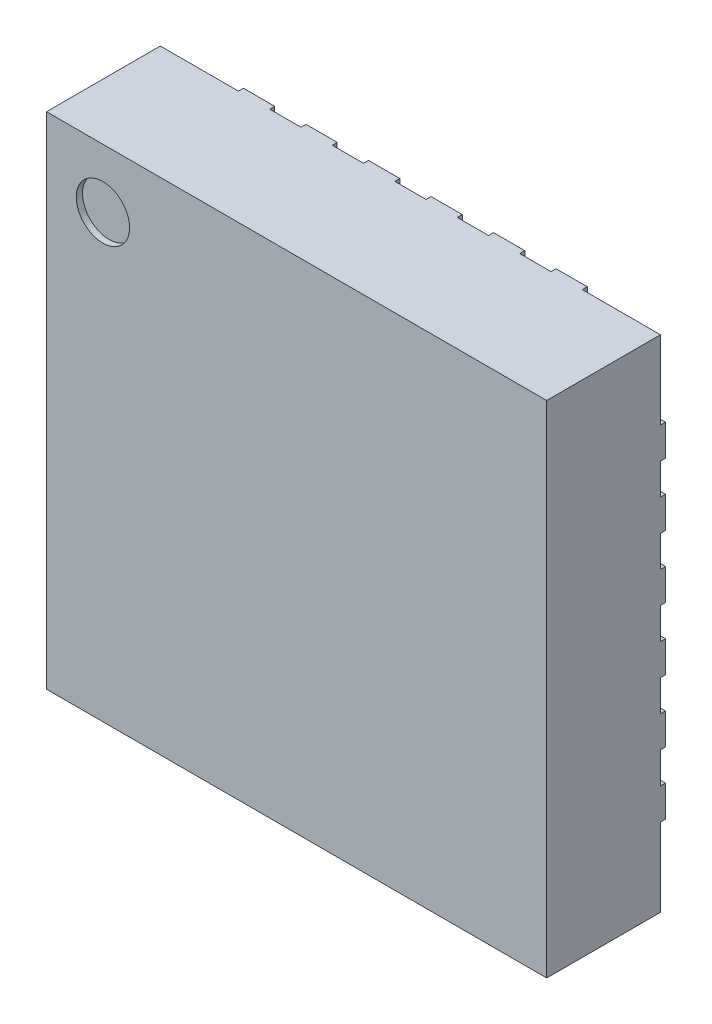
SolidWorks part; units mm, degrees
note: '?' marks a value the reader was unsure of.
ref_plane "Front Plane" through (0, 0, 0) normal (0, 0, 1) x (1, 0, 0)
ref_plane "Top Plane" through (0, 0, 0) normal (0, 1, 0) x (1, 0, 0)
ref_plane "Right Plane" through (0, 0, 0) normal (1, 0, 0) x (0, 0, -1)
sketch "Sketch1" plane through (0, 0, 0) normal (0, 0, 1) x (1, 0, 0)
  line L1 (-2, 2) -> (2, 2)
  line L2 (-2, 2) -> (-2, -2)
  line L3 (-2, -2) -> (2, -2)
  line L4 (2, 2) -> (2, -2)
  line L5 (-2, 2) -> (2, -2) construction
  line L6 (-2, -2) -> (2, 2) construction
  point P0 (0, 0)
  dimension "D1" = 4
  dimension "D2" = 4
extrude "Boss-Extrude1" add sketch "Sketch1" along normal blind 0.91 contours L4 L3 L2 L1
sketch "Sketch2" plane through (0, 0, 0) normal (0, 0, -1) x (-1, 0, 0)
  line L1 (-1.2, -1.3) -> (1.2, -1.3)
  line L2 (-1.3, -1.2) -> (-1.3, 1.2)
  line L3 (-1.2, 1.3) -> (1.2, 1.3)
  line L4 (1.3, -1.2) -> (1.3, 1.2)
  line L5 (-1.3, -1.3) -> (1.3, 1.3) construction
  line L6 (-1.3, 1.3) -> (1.3, -1.3) construction
  arc A0 (-1.2, -1.3) -> (-1.3, -1.2) centre (-1.2, -1.2) cw
  arc A1 (1.2, -1.3) -> (1.3, -1.2) centre (1.2, -1.2) ccw
  arc A2 (1.2, 1.3) -> (1.3, 1.2) centre (1.2, 1.2) cw
  arc A3 (-1.3, 1.2) -> (-1.2, 1.3) centre (-1.2, 1.2) cw
  point P0 (0, 0)
  dimension "D3" = 0.1
  dimension "D1" = 2.6
  dimension "D2" = 2.6
extrude "Boss-Extrude2" add sketch "Sketch2" along normal blind 0.04
sketch "Sketch3" plane through (0, 0, 0) normal (0, 0, -1) x (-1, 0, 0)
  line L0 (-1.625, 1.25) -> (-2.375, 1.25) construction
  line L1 (-1.625, 1.125) -> (-2.375, 1.125)
  line L2 (-1.625, 1.375) -> (-2.375, 1.375)
  line L3 (-2, 2) -> (-2, -2) construction
  line L6 (-2, 1.375) -> (-2, 1.125)
  arc A0 (-1.625, 1.125) -> (-1.625, 1.375) centre (-1.625, 1.25) ccw
  arc A1 (-2.375, 1.375) -> (-2.375, 1.125) centre (-2.375, 1.25) ccw
  point P2 (-2, 1.25)
  dimension "D2" = 0.25
  dimension "D1" = 1.25
  dimension "D3" = 0.375
extrude "Boss-Extrude3" add sketch "Sketch3" along normal up to surface (0.04 mm away) up to face at (0, 0, -0.04)
pattern_linear "LPattern1" count 6 spacing 0.5 along (0, -1, 0) of "Boss-Extrude3"
ref_axis "Axis1" through (0, 0, 0) along (0, 0, -1)?
pattern_circular "CirPattern1" count 4 over 360 about axis through (0, 0, 0) along (0, 0, 1) of "LPattern1", "Boss-Extrude3"
sketch "Sketch4" plane through (0, 0, 0.91) normal (0, 0, 1) x (1, 0, 0)
  circle A0 centre (-1.5492, 1.5283) radius 0.2132
extrude "Cut-Extrude1" cut sketch "Sketch4" against normal blind 0.05 contours A0
